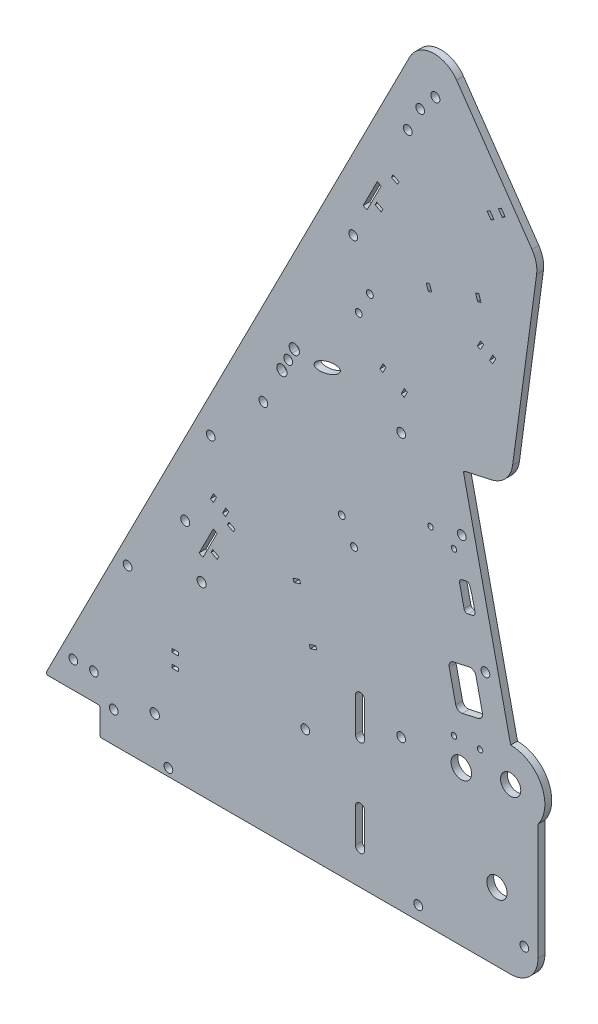
SolidWorks part; units mm, degrees
other "Markup1"
sketch "Sketch5"
ref_plane "Front Plane" through (0, 0, 0) normal (0, 0, 1) x (1, 0, 0)
ref_plane "Top Plane" through (0, 0, 0) normal (0, 1, 0) x (1, 0, 0)
ref_plane "Right Plane" through (0, 0, 0) normal (1, 0, 0) x (0, 0, -1)
sketch "Sketch1" plane through (0, 0, 0) normal (0, 0, 1) x (1, 0, 0)
  line L1 (228.6, -12.7) -> (228.6, 53.975)
  line L2 (178.7547, 351.4131) -> (0, 0)
  line L3 (228.6, 279.4) -> (178.7547, 351.4131)
  line L5 (0, 0) -> (25.4, 0)
  line L6 (25.4, 0) -> (25.4, -12.7)
  line L7 (25.4, -12.7) -> (228.6, -12.7)
  line L9 (215.9, 79.375) -> (193.9097, 178.5667)
  line L10 (193.9097, 178.5667) -> (215.6079, 183.377)
  line L11 (215.6079, 183.377) -> (228.6, 279.4)
  arc A0 (228.6, 53.975) -> (215.9, 79.375) centre (215.9, 63.5) ccw
  dimension "D7" = 12.7
  dimension "D8" = 76.2
  dimension "D10" = 31.75
  dimension "D2" = 292.1
  dimension "D3" = 25.4
  dimension "D4" = 215.9
  dimension "D5" = 394.2644
  dimension "D6" = 203.2
  dimension "D9" = 63.039
  dimension "D11" = 101.6
  dimension "D12" = 12.5
  dimension "D13" = 22.225
extrude "Boss-Extrude1" add sketch "Sketch1" along normal blind 3.175
sketch "Sketch2" plane through (0, 0, 3.175) normal (0, 0, 1) x (1, 0, 0)
  line L0 (178.7547, 351.4131) -> (0, 0) construction
  line L1 (25.4, -12.7) -> (228.6, -12.7) construction
  line L2 (215.9, 79.375) -> (193.9097, 178.5667) construction
  line L3 (193.9097, 178.5667) -> (215.6079, 183.377) construction
  line L4 (215.9, 79.375) -> (193.9097, 178.5667) construction
  line L5 (64.9432, 94.0578) -> (72.5445, 73.1732) construction
  line L6 (64.9432, 94.0578) -> (89.8317, 94.0578) construction
  line L10 (228.6, -12.7) -> (228.6, 53.975) construction
  circle A0 centre (64.9432, 94.0578) radius 2.0955
  circle A1 centre (180.975, 322.1643) radius 2.0955
  circle A2 centre (72.5445, 73.1732) radius 2.0955
  circle A3 centre (193.2078, 152.3944) radius 2.032
  circle A4 centre (215.9, 63.5) radius 4.699
  circle A7 centre (173.0375, -6.35) radius 2.032
  circle A8 centre (204.203, 102.7985) radius 2.032
  circle A26 centre (209.55, 19.05) radius 4.699
  arc A30 (228.6, 53.975) -> (215.9, 79.375) centre (215.9, 63.5) ccw construction
  circle A31 centre (165.1, 179.3875) radius 2.032
  dimension "D3" = 4.191
  dimension "D5" = 4.191
  dimension "D9" = 4.191
  dimension "D20" = 9.398
  dimension "D23" = 9.398
  dimension "D18" = 4.064
  dimension "D26" = 4.064
  dimension "D14" = 4.064
  dimension "D2" = 15.24
  dimension "D6" = 15.24
  dimension "D7" = 22.225
  dimension "D21" = 44.45
  dimension "D22" = 6.35
  dimension "D19" = 160.3375
  dimension "D24" = 44.45
  dimension "D25" = 6.35
  dimension "D27" = 25.4
  dimension "D28" = 50.8
  dimension "D29" = 6.35
  dimension "D17" = 6.35
  dimension "D33" = 55.5625
  dimension "D15" = 114.3
  dimension "D4" = 180.975
  dimension "D8" = 70
extrude "Cut-Extrude1" cut sketch "Sketch2" against normal through all
sketch "Sketch7" plane through (0, 0, 3.175) normal (0, 0, 1) x (1, 0, 0)
  line L0 (146.05, 3.175) -> (146.05, 19.05) construction
  line L1 (143.891, 3.175) -> (143.891, 19.05)
  line L2 (148.209, 3.175) -> (148.209, 19.05)
  line L3 (146.05, 47.625) -> (146.05, 63.5) construction
  line L4 (143.891, 47.625) -> (143.891, 63.5)
  line L5 (148.209, 47.625) -> (148.209, 63.5)
  line L6 (25.4, -12.7) -> (228.6, -12.7) construction
  line L12 (228.6, -12.7) -> (228.6, 53.975) construction
  line L13 (25.4, -12.7) -> (228.6, -12.7) construction
  arc A0 (143.891, 3.175) -> (148.209, 3.175) centre (146.05, 3.175) ccw
  arc A1 (148.209, 19.05) -> (143.891, 19.05) centre (146.05, 19.05) ccw
  arc A2 (143.891, 47.625) -> (148.209, 47.625) centre (146.05, 47.625) ccw
  arc A3 (148.209, 63.5) -> (143.891, 63.5) centre (146.05, 63.5) ccw
  circle A8 centre (50.8, 9.525) radius 2.159
  point P2 (146.05, 11.1125)
  point P9 (146.05, 55.5625)
  dimension "D1" = 4.318
  dimension "D5" = 4.318
  dimension "D2" = 15.875
  dimension "D3" = 15.875
  dimension "D4" = 44.45
  dimension "D6" = 95.25
  dimension "D7" = 82.55
  dimension "D8" = 15.875
  dimension "D9" = 22.225
extrude "Cut-Extrude2" cut sketch "Sketch7" against normal through all
sketch "Sketch10" plane through (0, 0, 3.175) normal (0, 0, 1) x (1, 0, 0)
  circle A1 centre (165.1, 57.15) radius 2.032
  circle A2 centre (120.65, 38.1) radius 2.032
  circle A3 centre (13.0465, 12.3347) radius 2.032
  circle A4 centre (22.5715, 12.3347) radius 2.032
  circle A5 centre (38.2114, 62.6398) radius 2.032
  dimension "D1" = 4.064
  dimension "D2" = 4.064
  dimension "D4" = 63.5
  dimension "D5" = 69.85
extrude "Cut-Extrude3" cut sketch "Sketch10" against normal up to next
fillet "Fillet1" radius 12.7 4 edges at (228.6, -12.7, 1.5875) (178.7547, 351.4131, 1.5875) (215.6079, 183.377, 1.5875) (228.6, 279.4, 1.5875)
fillet "Fillet2" radius 0.7937 4 edges at (25.4, -12.7, 1.5875) (25.4, 0, 1.5875) (193.9097, 178.5667, 1.5875) (0, 0, 1.5875)
sketch "Sketch12" plane through (0, 0, 3.175) normal (0, 0, 1) x (1, 0, 0)
  circle A0 centre (31.75, 1.5875) radius 2.032
  circle A1 centre (222.25, 1.5875) radius 2.032
  circle A2 centre (57.15, -9.2075) radius 2.032
  circle A3 centre (57.15, -9.2075) radius 2.286 construction
  dimension "D1" = 4.064
  dimension "D2" = 4.064
extrude "Cut-Extrude5" cut sketch "Sketch12" against normal through all
sketch "Sketch13" plane through (0, 0, 3.175) normal (0, 0, 1) x (1, 0, 0)
  line L2 (194.6847, 178.7385) -> (206.9592, 181.4597) construction
  line L5 (199.2434, 101.699) -> (189.6226, 145.0954) construction
  line L6 (189.6022, 69.9806) -> (201.7089, 70.5092) construction
  line L7 (186.8444, 98.9502) -> (199.2434, 101.699)
  line L8 (186.8444, 98.9502) -> (190.9676, 80.3518)
  line L9 (190.9676, 80.3518) -> (203.3665, 83.1006)
  line L10 (199.2434, 101.699) -> (203.3665, 83.1006)
  line L11 (189.6022, 69.9806) -> (190.9676, 80.3518) construction
  line L12 (201.7089, 70.5092) -> (203.3665, 83.1006) construction
  line L13 (215.9, 79.375) -> (194.0815, 177.7917) construction
  line L14 (178.7216, 148.5324) -> (189.6226, 145.0954) construction
  line L15 (195.1281, 134.9336) -> (193.4153, 134.5539)
  line L16 (192.209, 132.6604) -> (194.2706, 123.3612)
  line L17 (196.1641, 122.1549) -> (198.1091, 122.5861)
  line L18 (211.4332, 99.5233) -> (205.2337, 98.1489) construction
  line L19 (198.3765, 158.4184) -> (211.4332, 99.5233) construction
  circle A0 centre (189.6022, 69.9806) radius 1.27
  circle A1 centre (201.7089, 70.5092) radius 1.27
  circle A2 centre (178.7216, 148.5324) radius 1.27
  circle A3 centre (189.6226, 145.0954) radius 1.27
  arc A4 (199.3306, 124.402) -> (196.9796, 133.88) centre (134.9024, 113.4517) ccw
  arc A6 (199.4957, 103.5221) -> (189.2475, 149.7492) centre (134.9024, 113.4517) ccw construction
  arc A7 (195.1281, 134.9336) -> (196.9796, 133.88) centre (195.4717, 133.3837) cw
  arc A8 (198.1091, 122.5861) -> (199.3306, 124.402) centre (197.7655, 124.136) ccw
  arc A9 (194.2706, 123.3612) -> (196.1641, 122.1549) centre (195.8205, 123.7048) ccw
  arc A10 (193.4153, 134.5539) -> (192.209, 132.6604) centre (193.7589, 133.004) ccw
  point P26 (208.3335, 98.8361)
  point P31 (196.515, 135.2411)
  point P36 (194.6142, 121.8113)
  point P39 (191.8654, 134.2103)
  dimension "D7" = 2.54
  dimension "D16" = 1.5875
  dimension "D2" = 11.43
  dimension "D3" = 76.2
  dimension "D4" = 12.7
  dimension "D5" = 19.05
  dimension "D6" = 120
  dimension "D8" = 110
  dimension "D9" = 80
  dimension "D10" = 12.7
  dimension "D11" = 44.45
  dimension "D12" = 11.43
  dimension "D13" = 12.7
  dimension "D14" = 4.7625
  dimension "D15" = 38.1
extrude "Cut-Extrude6" cut sketch "Sketch13" against normal through all both and the other way through all
sketch "Sketch14" plane through (0, 0, 3.175) normal (0, 0, 1) x (1, 0, 0)
  line L0 (26.1937, -12.7) -> (215.9, -12.7) construction
  line L1 (228.6, 0) -> (228.6, 53.975) construction
  line L2 (112.7125, 182.5625) -> (101.1964, 159.9231) construction
  line L3 (169.1053, 332.4434) -> (0.5868, 1.1536) construction
  line L4 (112.7125, 182.5625) -> (136.864, 190.4279) construction
  line L5 (147.4827, 261.9243) -> (154.0469, 274.8287)
  line L6 (147.4827, 261.9243) -> (149.2654, 261.0175)
  line L7 (154.0469, 274.8287) -> (155.8295, 273.922)
  line L8 (149.2654, 261.0175) -> (155.8295, 273.922)
  line L9 (169.1053, 332.4434) -> (0.5868, 1.1536) construction
  line L10 (160.5905, 279.7801) -> (161.3102, 281.1951)
  line L11 (160.5905, 279.7801) -> (163.4204, 278.3406)
  line L12 (161.3102, 281.1951) -> (164.1402, 279.7556)
  line L13 (163.4204, 278.3406) -> (164.1402, 279.7556)
  line L14 (153.7897, 266.4104) -> (156.6196, 264.9709)
  line L15 (153.7897, 266.4104) -> (153.0699, 264.9954)
  line L16 (156.6196, 264.9709) -> (155.8998, 263.5559)
  line L17 (153.0699, 264.9954) -> (155.8998, 263.5559)
  line L19 (178.2697, 245.9923) -> (179.2404, 242.9693)
  line L20 (178.2697, 245.9923) -> (176.7582, 245.5069)
  line L21 (179.2404, 242.9693) -> (177.7289, 242.4839)
  line L22 (176.7582, 245.5069) -> (177.7289, 242.4839)
  line L24 (200.6096, 249.8308) -> (199.639, 252.8538)
  line L25 (200.6096, 249.8308) -> (202.1211, 250.3161)
  line L26 (199.639, 252.8538) -> (201.1505, 253.3391)
  line L27 (202.1211, 250.3161) -> (201.1505, 253.3391)
  line L34 (77.9534, 97.2255) -> (79.736, 96.3187)
  line L47 (77.9534, 97.2255) -> (71.3892, 84.3211)
  line L56 (79.736, 96.3187) -> (73.1718, 83.4143)
  line L57 (71.3892, 84.3211) -> (73.1718, 83.4143)
  line L58 (85.2167, 103.5918) -> (84.497, 102.1769)
  line L59 (85.2167, 103.5918) -> (88.0466, 102.1523)
  line L60 (84.497, 102.1769) -> (87.3269, 100.7374)
  line L61 (88.0466, 102.1523) -> (87.3269, 100.7374)
  line L62 (156.643, 199.3999) -> (158.0826, 202.2298)
  line L63 (156.643, 199.3999) -> (155.2281, 200.1197)
  line L64 (158.0826, 202.2298) -> (156.6676, 202.9496)
  line L65 (155.2281, 200.1197) -> (156.6676, 202.9496)
  line L66 (165.1328, 195.0814) -> (166.5723, 197.9113)
  line L67 (165.1328, 195.0814) -> (166.5478, 194.3617)
  line L68 (166.5723, 197.9113) -> (167.9873, 197.1916)
  line L69 (166.5478, 194.3617) -> (167.9873, 197.1916)
  line L78 (77.6961, 88.8072) -> (76.9764, 87.3922)
  line L79 (201.9154, 234.7497) -> (200.4759, 231.9198)
  line L80 (201.9154, 234.7497) -> (203.3303, 234.0299)
  line L81 (200.4759, 231.9198) -> (201.8908, 231.2)
  line L82 (203.3303, 234.0299) -> (201.8908, 231.2)
  line L83 (206.1357, 229.0407) -> (207.5752, 231.8707)
  line L84 (206.1357, 229.0407) -> (207.5507, 228.321)
  line L85 (207.5752, 231.8707) -> (208.9902, 231.1509)
  line L86 (207.5507, 228.321) -> (208.9902, 231.1509)
  line L88 (205.014, 288.3715) -> (206.821, 285.7609)
  line L89 (205.014, 288.3715) -> (206.3193, 289.275)
  line L90 (206.821, 285.7609) -> (208.1263, 286.6644)
  line L91 (206.3193, 289.275) -> (208.1263, 286.6644)
  line L92 (210.2352, 291.9855) -> (212.0422, 289.3749)
  line L93 (210.2352, 291.9855) -> (211.5405, 292.889)
  line L94 (212.0422, 289.3749) -> (213.3475, 290.2784)
  line L95 (211.5405, 292.889) -> (213.3475, 290.2784)
  line L96 (225.7968, 283.4499) -> (190.8675, 333.9133) construction
  line L97 (77.6961, 88.8072) -> (80.5261, 87.3677)
  line L98 (76.9764, 87.3922) -> (79.8063, 85.9527)
  line L99 (80.5261, 87.3677) -> (79.8063, 85.9527)
  line L100 (122.4534, 73.1037) -> (122.9512, 71.5963)
  line L101 (122.4534, 73.1037) -> (125.4682, 74.0993)
  line L102 (122.9512, 71.5963) -> (125.9661, 72.5919)
  line L103 (125.4682, 74.0993) -> (125.9661, 72.5919)
  line L104 (114.9173, 95.9228) -> (115.4151, 94.4154)
  line L105 (114.9173, 95.9228) -> (117.9322, 96.9185)
  line L106 (115.4151, 94.4154) -> (118.43, 95.411)
  line L107 (117.9322, 96.9185) -> (118.43, 95.411)
  line L108 (73.3338, 88.1438) -> (77.899, 97.1186) construction
  line L109 (75.1164, 87.2371) -> (79.6816, 96.2118) construction
  line L110 (76.2812, 89.5269) -> (86.5313, 84.313) construction
  line L111 (83.082, 102.8966) -> (93.3321, 97.6827) construction
  line L112 (121.934, 72.0825) -> (123.4755, 75.113) construction
  line L113 (127.9171, 72.8537) -> (123.4755, 75.113) construction
  line L114 (112.3753, 83.5081) -> (119.5388, 97.5909) construction
  line L115 (112.1491, 96.0767) -> (117.4079, 93.4017) construction
  line L116 (149.0052, 264.9173) -> (147.5544, 262.0651) construction
  line L117 (150.7878, 264.0106) -> (151.2099, 264.8403) construction
  line L118 (162.6248, 261.9162) -> (152.3747, 267.1302) construction
  line L119 (169.4256, 275.2859) -> (159.1755, 280.4999) construction
  line L120 (199.3876, 252.3597) -> (200.1584, 253.8749) construction
  line L121 (198.6169, 250.8445) -> (203.0585, 248.5852) construction
  line L122 (203.2698, 247.9167) -> (195.3067, 232.262) construction
  line L123 (180.2625, 244.9786) -> (175.0037, 247.6536) construction
  line L124 (178.1316, 240.7894) -> (185.2951, 254.8722) construction
  line L125 (190.7763, 226.1672) -> (185.5176, 228.8422) construction
  line L126 (58.7375, 39.6875) -> (61.9125, 39.6875)
  line L127 (58.7375, 39.6875) -> (58.7375, 38.1)
  line L128 (61.9125, 39.6875) -> (61.9125, 38.1)
  line L129 (58.7375, 38.1) -> (61.9125, 38.1)
  line L130 (58.7375, 33.3375) -> (61.9125, 33.3375)
  line L131 (58.7375, 33.3375) -> (58.7375, 31.75)
  line L132 (61.9125, 33.3375) -> (61.9125, 31.75)
  line L133 (58.7375, 31.75) -> (61.9125, 31.75)
  line L135 (78.0516, 111.4242) -> (76.6121, 108.5943)
  line L136 (78.0516, 111.4242) -> (79.4665, 110.7045)
  line L137 (76.6121, 108.5943) -> (78.027, 107.8745)
  line L138 (79.4665, 110.7045) -> (78.027, 107.8745)
  line L139 (82.2719, 105.7153) -> (83.7114, 108.5452)
  line L140 (82.2719, 105.7153) -> (83.6869, 104.9955)
  line L141 (83.7114, 108.5452) -> (85.1264, 107.8254)
  line L142 (83.6869, 104.9955) -> (85.1264, 107.8254)
  circle A0 centre (142.875, 247.65) radius 2.032
  circle A1 centre (112.7125, 182.5625) radius 2.032
  circle A2 centre (101.1964, 159.9231) radius 2.032
  circle A3 centre (150.594, 227.8985) radius 1.6 construction
  circle A4 centre (145.4254, 217.7376) radius 1.6 construction
  circle A5 centre (137.5592, 132.521) radius 1.6 construction
  circle A6 centre (143.2592, 122.6483) radius 1.6 construction
  circle A7 centre (150.594, 227.8985) radius 1.6
  circle A8 centre (145.4254, 217.7376) radius 1.6
  circle A9 centre (137.5592, 132.521) radius 1.6
  circle A10 centre (143.2592, 122.6483) radius 1.6
  arc A13 (0, 1.5875) -> (1.5875, 0) centre (1.5875, 1.5875) ccw construction
  ellipse E0 centre (109.8335, 176.9027) end of major axis (108.7539, 174.7802) minor radius 2.32 (108.7539, 174.7802) -> (110.9131, 179.0251) ccw construction
  ellipse E1 centre (109.8335, 176.9027) end of major axis (108.7539, 174.7802) minor radius 2.32 (108.7539, 174.7802) -> (110.9131, 179.0251) ccw
  ellipse E2 centre (130.8261, 188.4615) end of major axis (124.7883, 186.4952) minor radius 2.3812
  ellipse E3 centre (115.5915, 188.2223) end of major axis (114.5119, 186.0999) minor radius 2.32 (114.5119, 186.0999) -> (116.6711, 190.3448) ccw construction
  ellipse E4 centre (115.5915, 188.2223) end of major axis (114.5119, 186.0999) minor radius 2.32 (114.5119, 186.0999) -> (116.6711, 190.3448) ccw
  spline S0 degree 3 poles (603.8918, 1049.0657) (-166.9189, -675.3083) (147.8077, 168.3802) (110.3225, 179.2425) (110.1654, 179.2721) (109.6955, 179.3152) (109.3734, 179.2831) (108.9218, 179.1456) (108.7737, 179.0841) (108.4954, 178.9343) (108.365, 178.8464) (108.1219, 178.6442) (108.0097, 178.5297) (107.8134, 178.2839) (107.7278, 178.1512) (107.5834, 177.8672) (107.527, 177.7202) (107.4441, 177.4168) (107.4178, 177.2585) (107.3978, 176.9432) (107.4036, 176.7863) (107.4465, 176.4736) (107.4841, 176.3175) (107.5874, 176.0205) (107.6532, 175.8777) (107.8133, 175.6037) (107.9066, 175.4748) (114.8282, 167.6036) (173.9427, 200.577) (-567.4982, 911.3293) knots -15.287416 -15.287416 -15.287416 -15.287416 0.0625 0.0625 0.125 0.125 0.25 0.25 0.3125 0.3125 0.375 0.375 0.4375 0.4375 0.5 0.5 0.5625 0.5625 0.625 0.625 0.6875 0.6875 0.75 0.75 0.8125 0.8125 0.875 0.875 4.983329 4.983329 4.983329 4.983329 only from (110.9131, 179.0251) to (108.7539, 174.7802) construction
  spline S1 degree 3 poles (110.9131, 179.0251) (110.7727, 179.0965) (110.6265, 179.1544) (110.3225, 179.2425) (110.1654, 179.2721) (109.6955, 179.3152) (109.3734, 179.2831) (108.9218, 179.1456) (108.7737, 179.0841) (108.4954, 178.9343) (108.365, 178.8464) (108.1219, 178.6442) (108.0097, 178.5297) (107.8134, 178.2839) (107.7278, 178.1512) (107.5834, 177.8672) (107.527, 177.7202) (107.4441, 177.4168) (107.4178, 177.2585) (107.3978, 176.9432) (107.4036, 176.7863) (107.4465, 176.4736) (107.4841, 176.3175) (107.5874, 176.0205) (107.6532, 175.8777) (107.8133, 175.6037) (107.9066, 175.4748) (108.2178, 175.121) (108.4736, 174.9228) (108.7539, 174.7802) knots 0 0 0 0 0.0625 0.0625 0.125 0.125 0.25 0.25 0.3125 0.3125 0.375 0.375 0.4375 0.4375 0.5 0.5 0.5625 0.5625 0.625 0.625 0.6875 0.6875 0.75 0.75 0.8125 0.8125 0.875 0.875 1 1 1 1
  spline S2 degree 3 poles (-635.3332, 847.705) (160.0375, 206.8561) (120.8424, 181.1302) (113.9875, 186.4501) (113.8729, 186.5577) (113.5583, 186.9155) (113.3974, 187.1901) (113.2413, 187.6401) (113.2046, 187.793) (113.1618, 188.1044) (113.1558, 188.2648) (113.176, 188.5797) (113.2018, 188.7347) (113.2848, 189.0394) (113.3426, 189.1891) (113.5563, 189.6095) (113.7586, 189.8627) (114.1212, 190.1647) (114.2542, 190.2544) (114.5324, 190.4041) (114.6775, 190.4645) (114.9798, 190.5567) (115.1369, 190.5882) (115.4499, 190.6199) (115.6074, 190.6207) (115.9244, 190.5918) (116.0795, 190.5623) (125.0451, 187.9725) (125.4505, 134.6135) (-868.6048, 361.2821) knots -3.325634 -3.325634 -3.325634 -3.325634 0.0625 0.0625 0.125 0.125 0.25 0.25 0.3125 0.3125 0.375 0.375 0.4375 0.4375 0.5 0.5 0.625 0.625 0.6875 0.6875 0.75 0.75 0.8125 0.8125 0.875 0.875 0.9375 0.9375 4.586013 4.586013 4.586013 4.586013 only from (114.5119, 186.0999) to (116.6711, 190.3448) construction
  spline S3 degree 3 poles (114.5119, 186.0999) (114.3711, 186.1715) (114.2359, 186.2574) (113.9875, 186.4501) (113.8729, 186.5577) (113.5583, 186.9155) (113.3974, 187.1901) (113.2413, 187.6401) (113.2046, 187.793) (113.1618, 188.1044) (113.1558, 188.2648) (113.176, 188.5797) (113.2018, 188.7347) (113.2848, 189.0394) (113.3426, 189.1891) (113.5563, 189.6095) (113.7586, 189.8627) (114.1212, 190.1647) (114.2542, 190.2544) (114.5324, 190.4041) (114.6775, 190.4645) (114.9798, 190.5567) (115.1369, 190.5882) (115.4499, 190.6199) (115.6074, 190.6207) (115.9244, 190.5918) (116.0795, 190.5623) (116.3815, 190.4751) (116.53, 190.4166) (116.6711, 190.3448) knots 0 0 0 0 0.0625 0.0625 0.125 0.125 0.25 0.25 0.3125 0.3125 0.375 0.375 0.4375 0.4375 0.5 0.5 0.625 0.625 0.6875 0.6875 0.75 0.75 0.8125 0.8125 0.875 0.875 0.9375 0.9375 1 1 1 1
  point P179 (82.9794, 105.3554)
  dimension "D1" = 4.064
  dimension "D15" = 3.175
  dimension "D2" = 195.2625
  dimension "D3" = 115.8875
  dimension "D4" = 85.725
  dimension "D5" = 260.35
  dimension "D6" = 25.4
  dimension "D7" = 4.7625
  dimension "D8" = 12.7
  dimension "D9" = 19.05
  dimension "D10" = 45
  dimension "D11" = 6.858
  dimension "D12" = 7.62
  dimension "D13" = 3.175
  dimension "D14" = 1.5875
  dimension "D16" = 1.5875
  dimension "D17" = 1.5875
  dimension "D18" = 9.525
  dimension "D19" = 47.625
  dimension "D20" = 38.1
  dimension "D21" = 6.858
  dimension "D22" = 7.62
  dimension "D23" = 1.5875
  dimension "D24" = 3.175
  dimension "D25" = 1.5875
  dimension "D26" = 4.7625
  dimension "D27" = 4.7625
  dimension "D28" = 1.5875
  dimension "D29" = 3.175
  dimension "D30" = 9.525
  dimension "D31" = 4.7625
  dimension "D32" = 4.7625
  dimension "D33" = 1.5875
  dimension "D34" = 3.175
  dimension "D35" = 6.35
  dimension "D36" = 12.7
  dimension "D37" = 1.5875
  dimension "D38" = 3.175
  dimension "D39" = 9.525
  dimension "D40" = 57.15
  dimension "D41" = 44.45
  dimension "D42" = 1.5875
  dimension "D43" = 4.7625
  dimension "D44" = 3.175
extrude "Cut-Extrude7" cut sketch "Sketch14" against normal through all
sketch "Sketch15" plane through (0, 0, 3.175) normal (0, 0, 1) x (1, 0, 0)
  line L0 (169.1053, 332.4434) -> (0.5868, 1.1536) construction
  circle A0 centre (76.7868, 134.1481) radius 2.032
  circle A1 centre (173.9472, 313.9507) radius 2.032
  circle A2 centre (168.1892, 302.631) radius 2.032
  circle A3 centre (173.9472, 313.9507) radius 1.905 construction
  circle A4 centre (168.1892, 302.631) radius 1.905 construction
  dimension "D1" = 4.064
  dimension "D4" = 4.064
  dimension "D2" = 7.62
  dimension "D3" = 76.2
extrude "Cut-Extrude8" cut sketch "Sketch15" against normal through all
fillet "Fillet3" radius 2.54 4 edges at (199.2434, 101.699, 1.5875) (186.8444, 98.9502, 1.5875) (190.9676, 80.3518, 1.5875) (203.3665, 83.1006, 1.5875)
sketch "Sketch16" plane through (0, 0, 3.175) normal (0, 0, 1) x (1, 0, 0)
  line L0 (228.6, 0) -> (228.6, 53.975) construction
  line L1 (26.1937, -12.7) -> (215.9, -12.7) construction
  circle A0 centre (193.04, 58.801) radius 4.7625
  dimension "D1" = 9.525
  dimension "D2" = 35.56
  dimension "D3" = 71.501
extrude "Cut-Extrude9" cut sketch "Sketch16" against normal through all
equation "\"D6@Sketch2\"=\"D2@Sketch2\""
